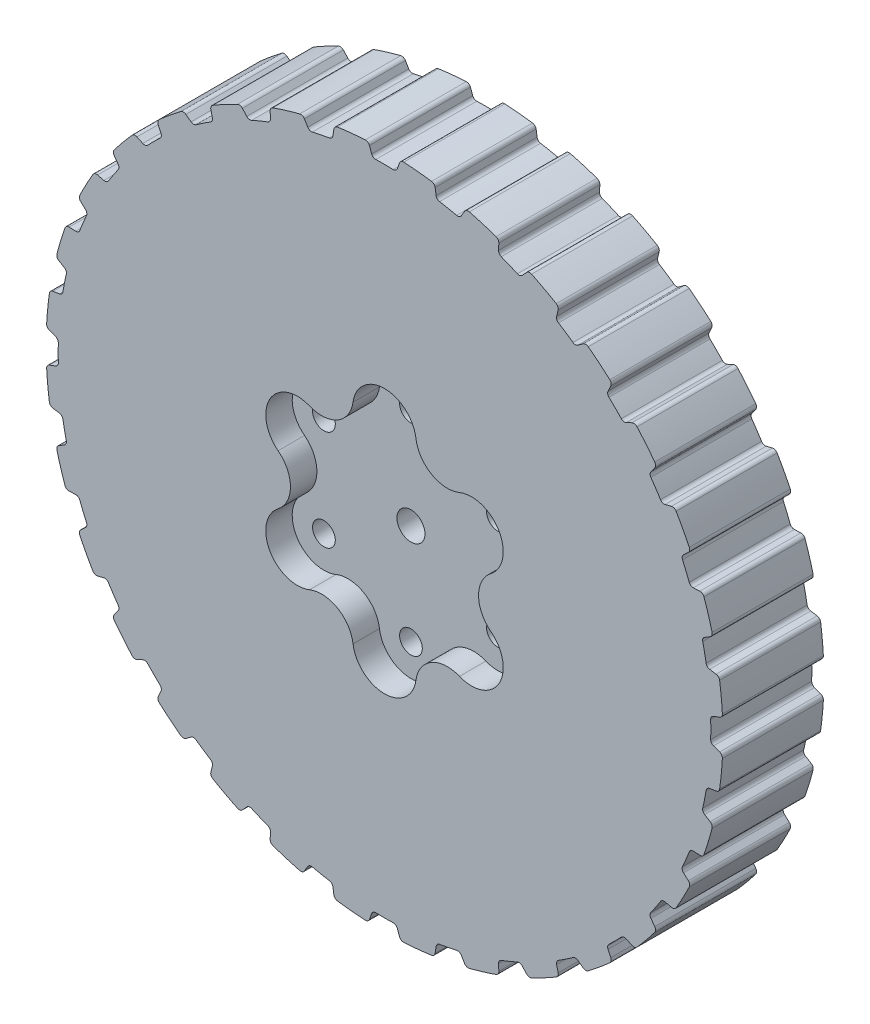
SolidWorks part; units mm, degrees
material "ABS"
ref_plane "正面" through (0, 0, 0) normal (0, 0, 1) x (1, 0, 0)
ref_plane "平面" through (0, 0, 0) normal (0, 1, 0) x (1, 0, 0)
ref_plane "右側面" through (0, 0, 0) normal (1, 0, 0) x (0, 0, -1)
sketch "ｽｹｯﾁ1" plane through (0, 0, 0) normal (0, 0, 1) x (1, 0, 0)
  line L96 (0, 0) -> (0, 19) construction
  arc A160 (5.9465, 19.7996) -> (-5.9465, 19.7996) centre (0, 19) ccw
  arc A161 (5.9465, 19.7996) -> (14.1737, 15.0496) centre (11.893, 20.5992) ccw
  arc A162 (20.1202, 4.75) -> (14.1737, 15.0496) centre (16.4545, 9.5) ccw
  arc A163 (20.1202, 4.75) -> (20.1202, -4.75) centre (23.7859, 0) ccw
  arc A164 (14.1737, -15.0496) -> (20.1202, -4.75) centre (16.4545, -9.5) ccw
  arc A165 (14.1737, -15.0496) -> (5.9465, -19.7996) centre (11.893, -20.5992) ccw
  arc A166 (-5.9465, -19.7996) -> (5.9465, -19.7996) centre (0, -19) ccw
  arc A167 (-5.9465, -19.7996) -> (-14.1737, -15.0496) centre (-11.893, -20.5992) ccw
  arc A168 (-20.1202, -4.75) -> (-14.1737, -15.0496) centre (-16.4545, -9.5) ccw
  arc A169 (-20.1202, -4.75) -> (-20.1202, 4.75) centre (-23.7859, 0) ccw
  arc A170 (-14.1737, 15.0496) -> (-20.1202, 4.75) centre (-16.4545, 9.5) ccw
  arc A171 (-14.1737, 15.0496) -> (-5.9465, 19.7996) centre (-11.893, 20.5992) ccw
  circle A172 centre (0, 0) radius 19 construction
  circle A173 centre (0, 0) radius 64.6806 construction
  circle A174 centre (0, 0) radius 63.9946
  point P443 (0, 0)
  dimension "D2" = 6
  dimension "D3" = 6
  dimension "D4" = 38
  dimension "D5" = 129.3611
  dimension "D6" = 127.9891
  dimension "D1" = 6
extrude "ﾎﾞｽ - 押し出し1" add sketch "ｽｹｯﾁ1" along normal blind 19.1 contours A174
sketch "ｽｹｯﾁ5" plane through (0, 0, 0) normal (0, 0, 1) x (1, 0, 0)
  line L0 (0, 0) -> (0, 63.9946) construction
  line L1 (-3.0467, 63.922) -> (-2.225, 61.6644) construction
  line L2 (3.0467, 63.922) -> (2.225, 61.6644) construction
  line L3 (-2.8442, 63.3658) -> (-2.4231, 62.2086)
  line L4 (2.4231, 62.2086) -> (2.8442, 63.3658)
  arc A0 (1.6499, 61.6825) -> (-1.6499, 61.6825) centre (0, 0) ccw
  arc A1 (3.6415, 63.8909) -> (-3.6415, 63.8909) centre (0, 0) ccw
  arc A2 (-2.8442, 63.3658) -> (-3.6415, 63.8909) centre (-3.596, 63.0922) ccw
  arc A3 (-2.4231, 62.2086) -> (-1.6499, 61.6825) centre (-1.6713, 62.4822) ccw
  arc A4 (2.4231, 62.2086) -> (1.6499, 61.6825) centre (1.6713, 62.4822) cw
  arc A5 (2.8442, 63.3658) -> (3.6415, 63.8909) centre (3.596, 63.0922) cw
  dimension "D2" = 127.9891
  dimension "D5" = 0.8
  dimension "D1" = 2.29
  dimension "D3" = 40
  dimension "D4" = 4.45
extrude "ｶｯﾄ - 押し出し2" cut sketch "ｽｹｯﾁ5" along normal through all
pattern_circular "円形ﾊﾟﾀｰﾝ1" count 32 over 360 about axis through (0, 0, 19.1) along (0, 0, -1) of "ｶｯﾄ - 押し出し2"
extrude "ｶｯﾄ - 押し出し1" cut sketch "ｽｹｯﾁ1<3>" against normal blind 5 from surface contours A161 A162 A163 A164 A165 A166 A167 A168 A169 A170 A171 A160 starting at face at (0, 0, 19.1)
sketch "ｽｹｯﾁ1<3>" plane through (0, 0, 0) normal (0, 0, 1) x (1, 0, 0) same geometry as "ｽｹｯﾁ1"
hole_wizard "M4 すきま穴1" positions "3Dｽｹｯﾁ2" profile "ｽｹｯﾁ3" hole size "M4" standard "JIS" end condition through all
sketch3d "3Dｽｹｯﾁ2"
  point P0 (0, 19, 0)
  point P2 (16.4545, 9.5, 0)
  point P4 (16.4545, -9.5, 0)
  point P6 (0, -19, 0)
  point P8 (-16.4545, -9.5, 0)
  point P10 (-16.4545, 9.5, 0)
sketch "ｽｹｯﾁ3" plane through (0, 19, 0) normal (1, 0, 0) x (0, 1, 0)
  line L0 (0, 0) -> (0, 19.1)
  line L1 (0, 19.1) -> (2.15, 19.1)
  line L2 (2.15, 19.1) -> (2.15, 0)
  line L5 (2.15, 0) -> (0, 0)
  line L11 (0, -6.35) -> (0, 107.95) construction
  dimension "通し穴の直径" = 4.3
  dimension "通し穴の深さ" = 19.1
hole_wizard "M5 すきま穴1" positions "3Dｽｹｯﾁ3" profile "ｽｹｯﾁ4" hole size "M5" standard "JIS" end condition through all
sketch3d "3Dｽｹｯﾁ3"
  point P4 (0, 0, 0)
sketch "ｽｹｯﾁ4" plane through (0, 0, 0) normal (1, 0, 0) x (0, 1, 0)
  line L0 (0, 0) -> (0, 19.1)
  line L1 (0, 19.1) -> (2.65, 19.1)
  line L2 (2.65, 19.1) -> (2.65, 0)
  line L5 (2.65, 0) -> (0, 0)
  line L11 (0, -6.35) -> (0, 107.95) construction
  dimension "通し穴の直径" = 5.3
  dimension "通し穴の深さ" = 19.1
equation "\"D5@ｽｹｯﾁ1\"=\"メインクローラプーリピッチ円直径\""
equation "\"D6@ｽｹｯﾁ1\"=\"メインクローラ歯先円直径\""
equation "\"D1@ｽｹｯﾁ5\"=\"メインクローラ歯たけ\""
equation "\"D2@ｽｹｯﾁ5\"=\"メインクローラ歯先円直径\""
equation "\"メインクローラピッチ\"= 0.5in"
equation "\"メインクローラベルト幅\"= 2in"
equation "\"メインクローラPLD\"= 0.686"
equation "\"メインクローラ歯たけ\"= \"2.29\""
equation "\"メインクローラベルトピッチ長\"= 49in"
equation "\"メインクローラプーリ歯数\"= 32"
equation "\"メインクローラプーリピッチ円直径\"= \"メインクローラピッチ\" * \"メインクローラプーリ歯数\" / pi"
equation "\"メインクローラ歯先円直径\"= \"メインクローラプーリピッチ円直径\" - 2 * \"メインクローラPLD\""
equation "\"フリッパピッチ\"= 0.5in"
equation "\"フリッパベルト幅\"= 0.75in"
equation "\"フリッパPLD\"= 0.686"
equation "\"フリッパ歯たけ\"= \"2.29\""
equation "\"フリッパベルトピッチ長\"= 33in"
equation "\"フリッパプーリ歯数_駆動側\"= 32"
equation "\"フリッパプーリピッチ円直径_駆動側\"= \"フリッパピッチ\" * \"フリッパプーリ歯数_駆動側\" / pi"
equation "\"フリッパ歯先円直径_駆動側\"= \"フリッパプーリピッチ円直径_駆動側\" - 2 * \"フリッパPLD\""
equation "\"フリッパ駆動ピッチ\"= 5"
equation "\"フリッパ駆動ベルト幅\"= 0.75in"
equation "\"フリッパ駆動PLD\"= 0.480"
equation "\"フリッパ駆動歯たけ\"= \"1.91\""
equation "\"フリッパ駆動ベルトピッチ長\"= 390"
equation "\"フリッパ駆動プーリ歯数_駆動側\"= 22"
equation "\"フリッパ駆動プーリ歯数_従動側\"= 44"
equation "\"フリッパ駆動プーリピッチ円直径_駆動側\"= \"フリッパ駆動ピッチ\" * \"フリッパ駆動プーリ歯数_駆動側\" / pi"
equation "\"フリッパ駆動プーリピッチ円直径_従動側\"= \"フリッパ駆動ピッチ\" * \"フリッパ駆動プーリ歯数_従動側\" / pi"
equation "\"フリッパ駆動歯先円直径_駆動側\"= \"フリッパ駆動プーリピッチ円直径_駆動側\" - 2 * \"フリッパ駆動PLD\""
equation "\"フリッパ駆動歯先円直径_従動側\"= \"フリッパ駆動プーリピッチ円直径_従動側\" - 2 * \"フリッパ駆動PLD\""
equation "\"回路ボックス横幅\" = 316"
equation "\"回路ボックス板厚\"= 6"
equation "\"接合溝\"= 1"
equation "\"ミル径\"= 1"
equation "\"板接合ねじ間隔\"= 30"
equation "\"フリッパ駆動ユニット+床板取付け位置\"= 16"
equation "\"タップ食いつき部長さ\"= 2"
equation "\"タップ深さ板接合部\"= 3"
equation "\"D1@円形ﾊﾟﾀｰﾝ1\"=\"フリッパプーリ歯数_駆動側\""
